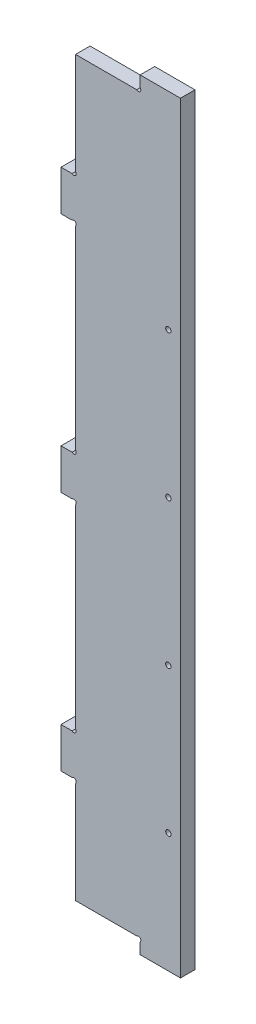
SolidWorks part; units mm, degrees
ref_plane "Front Plane" through (0, 0, 0) normal (0, 0, 1) x (1, 0, 0)
ref_plane "Top Plane" through (0, 0, 0) normal (0, 1, 0) x (1, 0, 0)
ref_plane "Right Plane" through (0, 0, 0) normal (1, 0, 0) x (0, 0, -1)
sketch "Sketch1" plane through (0, 0, 0) normal (0, 0, 1) x (1, 0, 0)
  line L0 (-961.2365, 328.9507) -> (-961.2365, 378.9507)
  line L8 (-943.2365, 807.9015) -> (-943.2365, 677.9015)
  line L9 (-943.2365, 677.9015) -> (-961.2365, 677.9015)
  line L10 (-961.2365, 627.9015) -> (-943.2365, 627.9015)
  line L11 (-943.2365, 627.9015) -> (-943.2365, 378.9507)
  line L12 (-943.2365, 378.9507) -> (-961.2365, 378.9507)
  line L13 (-961.2365, 627.9015) -> (-961.2365, 677.9015)
  line L18 (-414.1183, 825.9015) -> (-414.1183, 353.9507) construction
  line L19 (-961.2365, 353.9507) -> (-414.1183, 353.9507) construction
  line L20 (-943.2365, 807.9015) -> (-863.2365, 807.9015)
  line L21 (-863.2365, 807.9015) -> (-863.2365, 825.9015)
  line L22 (-863.2365, 825.9015) -> (-813.2365, 825.9015)
  line L23 (-813.2365, 825.9015) -> (-813.2365, 807.9015)
  line L24 (-813.2365, 807.9015) -> (-439.1183, 807.9015)
  line L25 (-439.1183, 807.9015) -> (-439.1183, 825.9015)
  line L26 (-843.2365, 603) -> (-843.2365, 0) construction
  line L28 (-439.1183, 825.9015) -> (-389.1183, 825.9015)
  line L29 (-788.166, 707.9015) -> (-779.041, 707.9015) construction
  line L30 (-439.1183, -118) -> (-389.1183, -118)
  line L31 (-439.1183, -100) -> (-439.1183, -118)
  line L32 (-813.2365, -100) -> (-439.1183, -100)
  line L33 (-813.2365, -118) -> (-813.2365, -100)
  line L34 (-863.2365, -118) -> (-813.2365, -118)
  line L35 (-863.2365, -100) -> (-863.2365, -118)
  line L36 (-943.2365, -100) -> (-863.2365, -100)
  line L37 (-961.2365, 80) -> (-961.2365, 30)
  line L38 (-943.2365, 328.9507) -> (-961.2365, 328.9507)
  line L39 (-943.2365, 80) -> (-943.2365, 328.9507)
  line L40 (-961.2365, 80) -> (-943.2365, 80)
  line L41 (-943.2365, 30) -> (-961.2365, 30)
  line L42 (-943.2365, -100) -> (-943.2365, 30)
  line L43 (-841.2365, 0) -> (-832.7445, 0) construction
  line L44 (115, -100) -> (115, 30)
  line L45 (115, 30) -> (133, 30)
  line L46 (133, 80) -> (115, 80)
  line L47 (115, 80) -> (115, 328.9507)
  line L48 (115, 328.9507) -> (133, 328.9507)
  line L49 (133, 80) -> (133, 30)
  line L50 (115, -100) -> (35, -100)
  line L51 (35, -100) -> (35, -118)
  line L52 (35, -118) -> (-15, -118)
  line L53 (-15, -118) -> (-15, -100)
  line L54 (-15, -100) -> (-389.1183, -100)
  line L55 (-389.1183, -100) -> (-389.1183, -118)
  line L56 (-389.1183, 807.9015) -> (-389.1183, 825.9015)
  line L57 (-15, 807.9015) -> (-389.1183, 807.9015)
  line L58 (-15, 825.9015) -> (-15, 807.9015)
  line L59 (35, 825.9015) -> (-15, 825.9015)
  line L60 (35, 807.9015) -> (35, 825.9015)
  line L61 (115, 807.9015) -> (35, 807.9015)
  line L62 (133, 627.9015) -> (133, 677.9015)
  line L63 (115, 378.9507) -> (133, 378.9507)
  line L64 (115, 627.9015) -> (115, 378.9507)
  line L65 (133, 627.9015) -> (115, 627.9015)
  line L66 (115, 677.9015) -> (133, 677.9015)
  line L67 (115, 807.9015) -> (115, 677.9015)
  line L68 (133, 328.9507) -> (133, 378.9507)
  line L69 (15, 603) -> (15, 0) construction
  point P24 (-961.2365, 353.9507)
  point P52 (-414.1183, -118)
  point P65 (133, 353.9507)
  dimension "D6" = 50
  dimension "D7" = 18
  dimension "D10" = 100
  dimension "D2" = 25
  dimension "D3" = 50
  dimension "D5" = 18
  dimension "D9" = 130
  dimension "D11" = 25
  dimension "D12" = 100
  dimension "D8" = 100
  dimension "D13" = 100
  dimension "D4" = 130
extrude "Boss-Extrude1" add sketch "Sketch1" along normal blind 18
sketch "Sketch2" plane through (0, 0, 0) normal (0, 0, -1) x (-1, 0, 0)
  line L0 (15, -118) -> (813.2365, -118)
  line L1 (813.2365, -118) -> (813.2365, 825.9015)
  line L2 (813.2365, 825.9015) -> (15, 825.9015)
  line L3 (15, 825.9015) -> (15, -118)
  line L4 (961.2365, 627.9015) -> (961.2365, 677.9015)
  line L5 (961.2365, 627.9015) -> (961.2365, 677.9015)
  line L6 (961.2365, 677.9015) -> (943.2365, 677.9015)
  line L7 (961.2365, 677.9015) -> (943.2365, 677.9015)
  line L64 (943.2365, 677.9015) -> (943.2365, 807.9015)
  line L65 (943.2365, 677.9015) -> (943.2365, 807.9015)
  line L66 (943.2365, 807.9015) -> (863.2365, 807.9015)
  line L67 (943.2365, 807.9015) -> (863.2365, 807.9015)
  line L68 (863.2365, 807.9015) -> (863.2365, 825.9015)
  line L69 (863.2365, 807.9015) -> (863.2365, 825.9015)
  line L70 (863.2365, 825.9015) -> (813.2365, 825.9015)
  line L71 (863.2365, 825.9015) -> (813.2365, 825.9015)
  line L72 (813.2365, 825.9015) -> (813.2365, 807.9015)
  line L73 (813.2365, 825.9015) -> (813.2365, 807.9015)
  line L74 (813.2365, 807.9015) -> (439.1183, 807.9015)
  line L75 (813.2365, 807.9015) -> (439.1183, 807.9015)
  line L76 (439.1183, 807.9015) -> (439.1183, 825.9015)
  line L77 (439.1183, 807.9015) -> (439.1183, 825.9015)
  line L78 (439.1183, 825.9015) -> (389.1183, 825.9015)
  line L79 (439.1183, 825.9015) -> (389.1183, 825.9015)
  line L80 (389.1183, 825.9015) -> (389.1183, 807.9015)
  line L81 (389.1183, 825.9015) -> (389.1183, 807.9015)
  line L82 (389.1183, 807.9015) -> (15, 807.9015)
  line L83 (389.1183, 807.9015) -> (15, 807.9015)
  line L84 (15, 807.9015) -> (15, 825.9015)
  line L85 (15, 807.9015) -> (15, 825.9015)
  line L86 (15, 825.9015) -> (-35, 825.9015)
  line L87 (15, 825.9015) -> (-35, 825.9015)
  line L88 (-35, 825.9015) -> (-35, 807.9015)
  line L89 (-35, 825.9015) -> (-35, 807.9015)
  line L90 (-35, 807.9015) -> (-115, 807.9015)
  line L91 (-35, 807.9015) -> (-115, 807.9015)
  line L92 (-115, 807.9015) -> (-115, 677.9015)
  line L93 (-115, 807.9015) -> (-115, 677.9015)
  line L94 (-115, 677.9015) -> (-133, 677.9015)
  line L95 (-115, 677.9015) -> (-133, 677.9015)
  line L96 (-133, 677.9015) -> (-133, 627.9015)
  line L97 (-133, 677.9015) -> (-133, 627.9015)
  line L98 (-133, 627.9015) -> (-115, 627.9015)
  line L99 (-133, 627.9015) -> (-115, 627.9015)
  line L100 (-115, 627.9015) -> (-115, 378.9507)
  line L101 (-115, 627.9015) -> (-115, 378.9507)
  line L102 (-115, 378.9507) -> (-133, 378.9507)
  line L103 (-115, 378.9507) -> (-133, 378.9507)
  line L104 (-133, 378.9507) -> (-133, 328.9507)
  line L105 (-133, 378.9507) -> (-133, 328.9507)
  line L106 (-133, 328.9507) -> (-115, 328.9507)
  line L107 (-133, 328.9507) -> (-115, 328.9507)
  line L108 (-115, 328.9507) -> (-115, 80)
  line L109 (-115, 328.9507) -> (-115, 80)
  line L110 (-115, 80) -> (-133, 80)
  line L111 (-115, 80) -> (-133, 80)
  line L112 (-133, 80) -> (-133, 30)
  line L113 (-133, 80) -> (-133, 30)
  line L114 (-133, 30) -> (-115, 30)
  line L115 (-133, 30) -> (-115, 30)
  line L116 (-115, 30) -> (-115, -100)
  line L117 (-115, 30) -> (-115, -100)
  line L118 (-115, -100) -> (-35, -100)
  line L119 (-115, -100) -> (-35, -100)
  line L120 (-35, -100) -> (-35, -118)
  line L121 (-35, -100) -> (-35, -118)
  line L122 (-35, -118) -> (15, -118)
  line L123 (-35, -118) -> (15, -118)
  line L124 (15, -118) -> (15, -100)
  line L125 (15, -118) -> (15, -100)
  line L126 (15, -100) -> (389.1183, -100)
  line L127 (15, -100) -> (389.1183, -100)
  line L128 (389.1183, -100) -> (389.1183, -118)
  line L129 (389.1183, -100) -> (389.1183, -118)
  line L130 (389.1183, -118) -> (439.1183, -118)
  line L131 (389.1183, -118) -> (439.1183, -118)
  line L132 (439.1183, -118) -> (439.1183, -100)
  line L133 (439.1183, -118) -> (439.1183, -100)
  line L134 (439.1183, -100) -> (813.2365, -100)
  line L135 (439.1183, -100) -> (813.2365, -100)
  line L136 (813.2365, -100) -> (813.2365, -118)
  line L137 (813.2365, -100) -> (813.2365, -118)
  line L138 (813.2365, -118) -> (863.2365, -118)
  line L139 (813.2365, -118) -> (863.2365, -118)
  line L140 (863.2365, -118) -> (863.2365, -100)
  line L141 (863.2365, -118) -> (863.2365, -100)
  line L142 (863.2365, -100) -> (943.2365, -100)
  line L143 (863.2365, -100) -> (943.2365, -100)
  line L144 (943.2365, -100) -> (943.2365, 30)
  line L145 (943.2365, -100) -> (943.2365, 30)
  line L146 (943.2365, 30) -> (961.2365, 30)
  line L147 (943.2365, 30) -> (961.2365, 30)
  line L148 (961.2365, 30) -> (961.2365, 80)
  line L149 (961.2365, 30) -> (961.2365, 80)
  line L150 (961.2365, 80) -> (943.2365, 80)
  line L151 (961.2365, 80) -> (943.2365, 80)
  line L152 (943.2365, 80) -> (943.2365, 328.9507)
  line L153 (943.2365, 80) -> (943.2365, 328.9507)
  line L154 (943.2365, 328.9507) -> (961.2365, 328.9507)
  line L155 (943.2365, 328.9507) -> (961.2365, 328.9507)
  line L156 (961.2365, 328.9507) -> (961.2365, 378.9507)
  line L157 (961.2365, 328.9507) -> (961.2365, 378.9507)
  line L158 (961.2365, 378.9507) -> (943.2365, 378.9507)
  line L159 (961.2365, 378.9507) -> (943.2365, 378.9507)
  line L160 (943.2365, 378.9507) -> (943.2365, 627.9015)
  line L161 (943.2365, 378.9507) -> (943.2365, 627.9015)
  line L162 (943.2365, 627.9015) -> (961.2365, 627.9015)
  line L163 (943.2365, 627.9015) -> (961.2365, 627.9015)
  dimension "D1" = 0
extrude "Cut-Extrude1" cut sketch "Sketch2" against normal through all contours L129 L127 L3 L0 | L135 L133 L0 L1 | L133 L135 L1 L2 L3 L127 L129 L0 region at (-202.0591, -109, 0) region at (-414.1183, 353.9507, 0) region at (-626.1774, -109, 0)
sketch "Sketch3" plane through (0, 0, 0) normal (0, 0, -1) x (-1, 0, 0)
  line L0 (15, 603) -> (15, 0) construction
  line L1 (813.2365, 573) -> (15, 573)
  line L2 (813.2365, 573) -> (813.2365, 562.1515)
  line L3 (813.2365, 562.1515) -> (15, 562.1515)
  line L4 (15, 573) -> (15, 562.1515)
  line L5 (215.9071, 592.1515) -> (206.7821, 592.1515) construction
  dimension "D1" = 30
  dimension "D2" = 10.8485
extrude "Boss-Extrude2" [suppressed] add sketch "Sketch3" against normal up to surface (18 mm away) up to face at (-919.6365, 353.9507, 18)
sketch "Sketch6" plane through (0, 0, 18) normal (0, 0, 1) x (1, 0, 0)
  line L0 (-828.2365, 603) -> (-828.2365, 0) construction
  line L1 (-828.2365, 603) -> (-828.2365, 0)
  line L2 (0, 603) -> (0, 0) construction
  line L3 (0, 603) -> (0, 0)
hole_wizard "M6 Clearance Hole1" positions "Sketch7" profile "Sketch8" hole size "M6" standard "ISO" end condition through all
sketch "Sketch7" plane through (0, 0, 18) normal (0, 0, 1) x (1, 0, 0)
  line L0 (-828.2365, 603) -> (-828.2365, 0) construction
  line L1 (0, 603) -> (0, 0) construction
  line L2 (0, 30) -> (-828.2365, 30) construction
  line L4 (0, 210) -> (-828.2365, 210) construction
  line L5 (0, 390) -> (-828.2365, 390) construction
  line L6 (0, 570) -> (-828.2365, 570) construction
  point P0 (-828.2365, 30)
  point P4 (0, 30)
  point P18 (-828.2365, 210)
  point P19 (0, 210)
  point P22 (-828.2365, 390)
  point P23 (0, 390)
  point P26 (-828.2365, 570)
  point P27 (0, 570)
  dimension "D1" = 30
  dimension "D2" = 4
sketch "Sketch8" plane through (-828.2365, 30, 18) normal (1, 0, 0) x (0, -1, 0)
  line L0 (0, 0) -> (0, 18)
  line L1 (0, 18) -> (3.3, 18)
  line L2 (3.3, 18) -> (3.3, 0)
  line L5 (3.3, 0) -> (0, 0)
  line L11 (0, -6.35) -> (0, 107.95) construction
  dimension "Thru Hole Dia." = 6.6
  dimension "Thru Hole Depth" = 18
sketch "Sketch9" plane through (0, 0, 0) normal (0, 0, -1) x (-1, 0, 0)
  line L0 (863.2365, -100) -> (881.2365, -118) construction
  line L1 (943.2365, 30) -> (961.2365, 12) construction
  line L2 (961.2365, 55) -> (976.842, 55) construction
  line L3 (961.2365, 80) -> (961.2365, 30) construction
  line L4 (943.2365, 80) -> (961.2365, 98) construction
  line L5 (961.2365, 353.9507) -> (990.1537, 353.9507) construction
  line L6 (961.2365, 378.9507) -> (961.2365, 328.9507) construction
  line L7 (943.2365, 328.9507) -> (961.2365, 310.9507) construction
  line L8 (961.2365, 353.9507) -> (976.842, 353.9507) construction
  line L9 (943.2365, 378.9507) -> (961.2365, 396.9507) construction
  line L10 (961.2365, 652.9015) -> (990.1537, 652.9015) construction
  line L11 (943.2365, 627.9015) -> (961.2365, 609.9015) construction
  line L12 (961.2365, 652.9015) -> (976.842, 652.9015) construction
  line L13 (943.2365, 677.9015) -> (961.2365, 695.9015) construction
  line L14 (863.2365, 807.9015) -> (881.2365, 825.9015) construction
  line L15 (15, 353.9507) -> (813.2365, 353.9507) construction
  line L16 (15, 825.9015) -> (15, -118) construction
  line L17 (813.2365, -118) -> (813.2365, 825.9015) construction
  line L18 (414.1183, 353.9507) -> (414.1183, 476.7491) construction
  line L19 (-35, 807.9015) -> (-53, 825.9015) construction
  line L20 (-115, 677.9015) -> (-133, 695.9015) construction
  line L21 (-133, 652.9015) -> (-148.6055, 652.9015) construction
  line L22 (-115, 627.9015) -> (-133, 609.9015) construction
  line L23 (-133, 652.9015) -> (-161.9172, 652.9015) construction
  line L24 (-115, 378.9507) -> (-133, 396.9507) construction
  line L25 (-133, 353.9507) -> (-148.6055, 353.9507) construction
  line L26 (-115, 328.9507) -> (-133, 310.9507) construction
  line L27 (-133, 353.9507) -> (-161.9172, 353.9507) construction
  line L28 (-115, 80) -> (-133, 98) construction
  line L29 (-133, 55) -> (-148.6055, 55) construction
  line L30 (-115, 30) -> (-133, 12) construction
  line L31 (-35, -100) -> (-53, -118) construction
  circle A0 centre (865.3578, -102.1213) radius 3
  circle A1 centre (945.3578, 27.8787) radius 3
  circle A2 centre (945.3578, 82.1213) radius 3
  circle A3 centre (945.3578, 326.8294) radius 3
  circle A4 centre (945.3578, 381.0721) radius 3
  circle A5 centre (945.3578, 625.7802) radius 3
  circle A6 centre (945.3578, 680.0228) radius 3
  circle A7 centre (865.3578, 810.0228) radius 3
  circle A8 centre (-37.1213, 810.0228) radius 3
  circle A9 centre (-117.1213, 680.0228) radius 3
  circle A10 centre (-117.1213, 625.7802) radius 3
  circle A11 centre (-117.1213, 381.0721) radius 3
  circle A12 centre (-117.1213, 326.8294) radius 3
  circle A13 centre (-117.1213, 82.1213) radius 3
  circle A14 centre (-117.1213, 27.8787) radius 3
  circle A15 centre (-37.1213, -102.1213) radius 3
  dimension "D1" = 6
  dimension "D2" = 6
  dimension "D3" = 6
  dimension "D4" = 6
extrude "Cut-Extrude2" cut sketch "Sketch9" against normal blind 30
sketch "Sketch10" plane through (0, 0, 0) normal (0, 0, -1) x (-1, 0, 0)
  line L1 (207.7244, -228.6449) -> (-354.6225, -228.6449)
  line L2 (207.7244, -228.6449) -> (207.7244, 890.659)
  line L3 (207.7244, 890.659) -> (-354.6225, 890.659)
  line L4 (-354.6225, -228.6449) -> (-354.6225, 890.659)
extrude "Cut-Extrude3" cut sketch "Sketch10" against normal blind 19
equation "\"fingerlenght\"=50"
equation "\"D6@Sketch1\"=\"fingerlenght\""
equation "\"fingerendclearance\"=130"
equation "\"osbthickness\"=18"
equation "\"D7@Sketch1\"=\"osbthickness\""
equation "\"D2@Sketch1\"=\"fingerlenght\"/2"
equation "\"D3@Sketch1\"=\"fingerlenght\""
equation "\"D5@Sketch1\"=\"osbthickness\""
equation "\"D9@Sketch1\"=\"fingerendclearance\""
equation "\"D11@Sketch1\"=\"fingerlenght\"/2"
equation "\"wallclearance\"=100"
equation "\"D12@Sketch1\"=\"wallclearance\""
equation "\"D10@Sketch1\"=\"wallclearance\""
equation "\"D13@Sketch1\"=\"wallclearance\""
